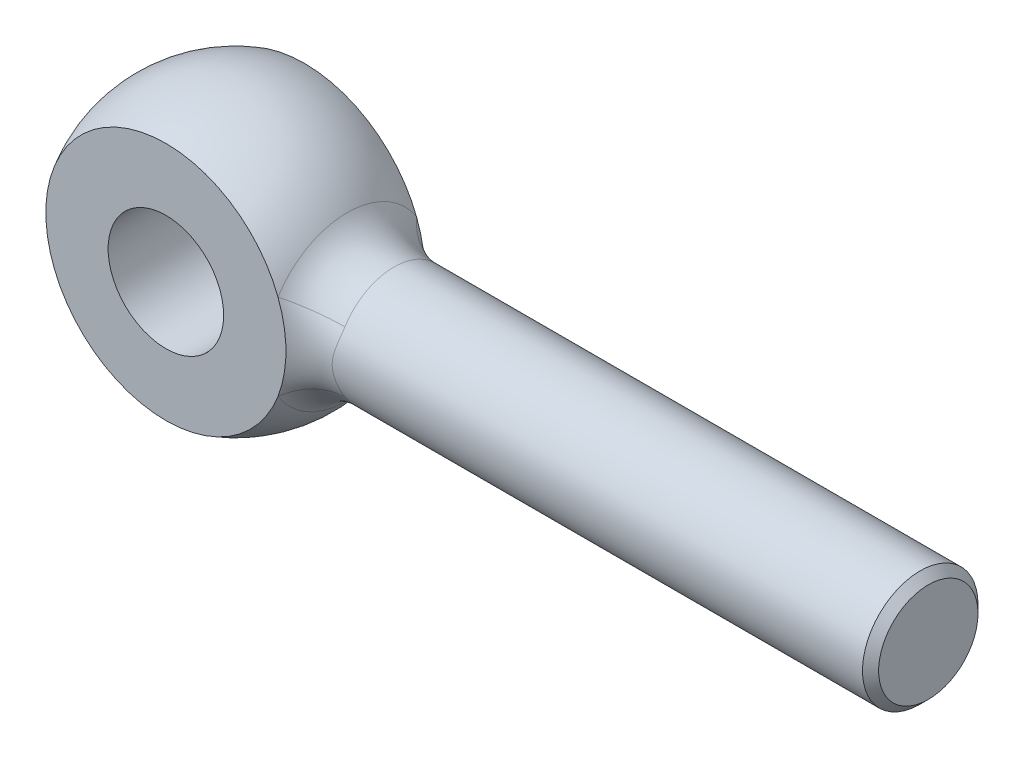
SolidWorks part; units mm, degrees
ref_plane "Přední rovina" through (0, 0, 0) normal (0, 0, 1) x (1, 0, 0)
ref_plane "Vrchní rovina" through (0, 0, 0) normal (0, 1, 0) x (1, 0, 0)
ref_plane "Pravá rovina" through (0, 0, 0) normal (1, 0, 0) x (0, 0, -1)
sketch "Skica1" plane through (0, 0, 0) normal (1, 0, 0) x (0, 0, -1)
  line L0 (0, 6) -> (0, 0) construction
  line L1 (-3, 5.1962) -> (-3, 0)
  line L2 (0, 0) -> (0, -6) construction
  line L3 (3, 0) -> (3, 5.1962)
  line L4 (3, 0) -> (-3, 0)
  arc A1 (3, 5.1962) -> (-3, 5.1962) centre (0, 0) ccw
  dimension "D" = 12
  dimension "g" = 6
revolve "Otočit kolem osy1" add sketch "Skica1" angle 360 about L4
sketch "Skica2" plane through (0, 0, 3) normal (0, 0, 1) x (1, 0, 0)
  circle A0 centre (0, 0) radius 2.5
  dimension "d6" = 5
extrude "Odebrat vysunutím1" cut sketch "Skica2" against normal through all
ref_plane "Rovina1" through (30, 0, 0) normal (1, 0, 0) x (0, 0, -1)
sketch "Skica3" plane through (30, 0, 0) normal (1, 0, 0) x (0, 0, -1)
  circle A0 centre (0, 0) radius 2.5
  dimension "M" = 5
extrude "Vysunout1" add sketch "Skica3" against normal up to next
cosmetic thread "Kosmetický závit1" parameters "b"=16, "D2"=4.25
fillet "Zaoblit1" radius 2.5 1 edges at (5.4544, 0, 2.5)
chamfer "Zkosit1" distance 0.35 angle 45 1 edges at (30, 0, -2.5)
equation "\"D1@Zkosit1\" = 0.07 * \"M@Skica3\""
equation "\"D2@Kosmetický závit1\" = 0.85 * \"M@Skica3\""
